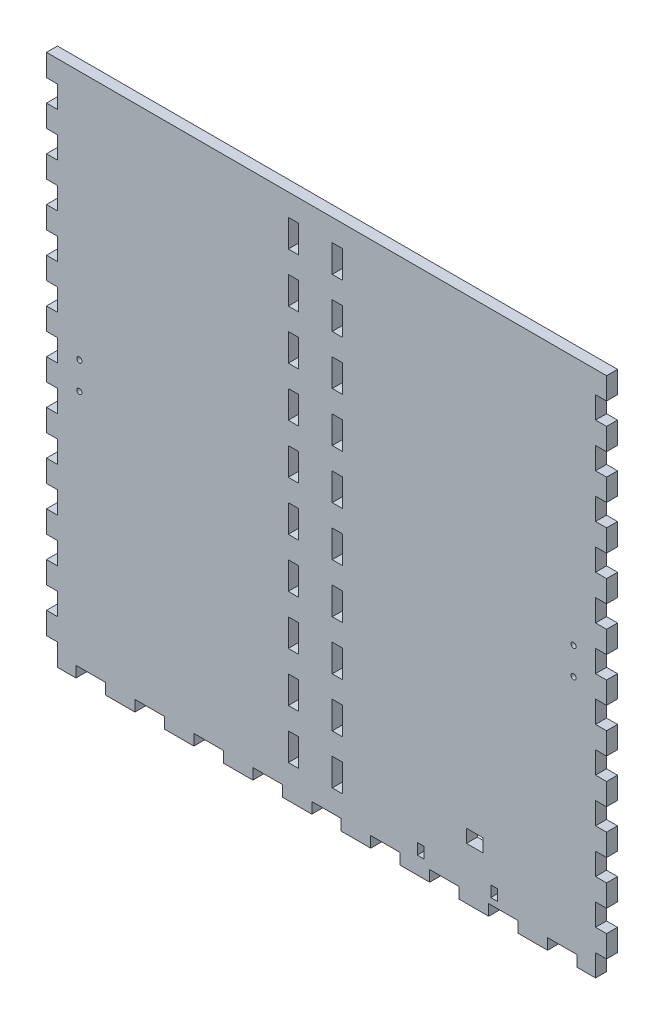
SolidWorks part; units mm, degrees
material "Acrylic (Medium-high impact)"
ref_plane "Front Plane" through (0, 0, 0) normal (0, 0, 1) x (1, 0, 0)
ref_plane "Top Plane" through (0, 0, 0) normal (0, 1, 0) x (1, 0, 0)
ref_plane "Right Plane" through (0, 0, 0) normal (1, 0, 0) x (0, 0, -1)
sketch "Sketch1" plane through (0, 0, 0) normal (0, 1, 0) x (1, 0, 0)
  line L1 (-161.925, 69.85) -> (161.925, 69.85)
  line L2 (-161.925, 69.85) -> (-161.925, -69.85)
  line L3 (-161.925, -69.85) -> (161.925, -69.85)
  line L4 (161.925, 69.85) -> (161.925, -69.85)
  point P4 (-161.925, 0)
  point P6 (0, 69.85)
  dimension "D1" = 139.7
  dimension "D2" = 323.85
extrude "Boss-Extrude1" add sketch "Sketch1" along normal blind 6.35
sketch "Sketch2" plane through (0, 6.35, 0) normal (0, 1, 0) x (1, 0, 0)
  line L0 (161.925, -69.85) -> (161.925, 69.85) construction
  line L1 (-161.925, 69.85) -> (161.925, 69.85)
  line L2 (-161.925, 69.85) -> (-161.925, -69.85)
  line L3 (-161.925, -69.85) -> (161.925, -69.85)
  line L4 (161.925, 69.85) -> (161.925, -69.85)
  line L5 (-161.925, -69.85) -> (161.925, -69.85) construction
  line L7 (-155.575, 63.5) -> (155.575, 63.5)
  line L8 (-155.575, 63.5) -> (-155.575, -63.5)
  line L9 (-155.575, -63.5) -> (155.575, -63.5)
  line L10 (155.575, 63.5) -> (155.575, -63.5)
  point P7 (-155.575, 0)
  point P14 (-161.925, 0)
  point P15 (0, -63.5)
  point P16 (0, -69.85)
  point P17 (155.575, 0)
  point P18 (161.925, 0)
  dimension "D1" = 6.35
  dimension "D2" = 6.35
extrude "Boss-Extrude2" add sketch "Sketch2" along normal blind 298.45
sketch "Sketch3" plane through (0, 0, 69.85) normal (0, 0, 1) x (1, 0, 0)
  line L0 (0, 304.8) -> (0, 0) construction
  line L2 (-155.575, 6.35) -> (155.575, 6.35) construction
  line L4 (-3.302, 283.21) -> (-3.302, 6.35)
  line L5 (-3.302, 6.35) -> (3.302, 6.35)
  line L6 (3.302, 292.354) -> (3.302, 6.35)
  line L7 (3.302, 292.354) -> (-16.256, 292.354)
  line L9 (-5.842, 285.75) -> (-16.256, 285.75)
  line L10 (-16.256, 292.354) -> (-16.256, 285.75)
  line L11 (3.302, 101.6) -> (16.002, 101.6) construction
  line L12 (-161.925, 0) -> (161.925, 0) construction
  line L13 (12.827, 88.9) -> (12.827, 101.6) construction
  line L14 (9.652, 88.9) -> (16.002, 88.9)
  line L15 (9.652, 88.9) -> (9.652, 71.9667)
  line L16 (9.652, 71.9667) -> (16.002, 71.9667)
  line L17 (16.002, 88.9) -> (16.002, 71.9667)
  line L18 (9.652, 42.3333) -> (16.002, 42.3333)
  line L19 (9.652, 42.3333) -> (9.652, 59.2667)
  line L20 (9.652, 59.2667) -> (16.002, 59.2667)
  line L21 (16.002, 42.3333) -> (16.002, 59.2667)
  line L26 (9.652, 29.6333) -> (16.002, 29.6333)
  line L27 (9.652, 29.6333) -> (9.652, 12.7)
  line L28 (9.652, 12.7) -> (16.002, 12.7)
  line L29 (16.002, 29.6333) -> (16.002, 12.7)
  line L30 (12.827, 59.2667) -> (12.827, 71.9667) construction
  line L31 (12.827, 29.6333) -> (12.827, 42.3333) construction
  line L32 (12.827, 12.7) -> (12.827, 0) construction
  line L33 (-161.925, 304.8) -> (161.925, 304.8) construction
  arc A0 (-3.302, 283.21) -> (-5.842, 285.75) centre (-5.842, 283.21) ccw
  point P4 (0, 0)
  point P5 (0, 6.35)
  dimension "D5" = 2.54
  dimension "D1" = 6.604
  dimension "D2" = 12.954
  dimension "D3" = 6.604
  dimension "D4" = 286.004
  dimension "D6" = 101.6
  dimension "D7" = 12.7
  dimension "D8" = 12.7
  dimension "D9" = 6.35
extrude "Door Slot" cut sketch "Sketch3" against normal blind 12.7
sketch "Sketch4" plane through (0, 0, -63.5) normal (0, 0, 1) x (1, 0, 0)
  line L0 (-161.925, 304.8) -> (161.925, 304.8) construction
  line L1 (-22.098, 304.8) -> (-16.256, 304.8)
  line L2 (-22.098, 304.8) -> (-22.098, 6.35)
  line L3 (-22.098, 6.35) -> (-16.256, 6.35)
  line L4 (-16.256, 304.8) -> (-16.256, 6.35)
  line L5 (6.223, 263.525) -> (6.223, 247.65) construction
  line L6 (-16.256, 292.354) -> (-16.256, 285.75) construction
  line L7 (3.302, 304.8) -> (9.144, 304.8)
  line L8 (3.302, 304.8) -> (3.302, 6.35)
  line L9 (3.302, 6.35) -> (9.144, 6.35)
  line L10 (9.144, 304.8) -> (9.144, 6.35)
  line L11 (155.575, 6.35) -> (-155.575, 6.35) construction
  line L12 (3.302, 6.35) -> (3.302, 292.354) construction
  line L13 (-16.256, 304.8) -> (-22.098, 304.8)
  line L14 (-16.256, 304.8) -> (-16.256, 292.1)
  line L15 (-16.256, 292.1) -> (-22.098, 292.1)
  line L16 (-22.098, 304.8) -> (-22.098, 292.1)
  line L17 (-16.256, 276.225) -> (-22.098, 276.225)
  line L18 (-16.256, 276.225) -> (-16.256, 263.525)
  line L19 (-16.256, 263.525) -> (-22.098, 263.525)
  line L20 (-22.098, 276.225) -> (-22.098, 263.525)
  line L21 (-22.098, 6.35) -> (-16.256, 6.35)
  line L22 (-22.098, 6.35) -> (-22.098, 19.05)
  line L23 (-22.098, 19.05) -> (-16.256, 19.05)
  line L24 (-16.256, 6.35) -> (-16.256, 19.05)
  line L25 (-22.098, 34.925) -> (-16.256, 34.925)
  line L26 (-22.098, 34.925) -> (-22.098, 47.625)
  line L27 (-22.098, 47.625) -> (-16.256, 47.625)
  line L28 (-16.256, 34.925) -> (-16.256, 47.625)
  line L29 (-22.098, 92.075) -> (-16.256, 92.075)
  line L30 (-22.098, 92.075) -> (-22.098, 104.775)
  line L31 (-22.098, 104.775) -> (-16.256, 104.775)
  line L32 (-16.256, 92.075) -> (-16.256, 104.775)
  line L33 (-22.098, 149.225) -> (-16.256, 149.225)
  line L34 (-22.098, 149.225) -> (-22.098, 161.925)
  line L35 (-22.098, 161.925) -> (-16.256, 161.925)
  line L36 (-16.256, 149.225) -> (-16.256, 161.925)
  line L37 (-22.098, 177.8) -> (-16.256, 177.8)
  line L38 (-22.098, 177.8) -> (-22.098, 190.5)
  line L39 (-22.098, 190.5) -> (-16.256, 190.5)
  line L40 (-16.256, 177.8) -> (-16.256, 190.5)
  line L41 (-22.098, 206.375) -> (-16.256, 206.375)
  line L42 (-22.098, 206.375) -> (-22.098, 219.075)
  line L43 (-22.098, 219.075) -> (-16.256, 219.075)
  line L44 (-16.256, 206.375) -> (-16.256, 219.075)
  line L45 (-22.098, 234.95) -> (-16.256, 234.95)
  line L46 (-22.098, 234.95) -> (-22.098, 247.65)
  line L47 (-22.098, 247.65) -> (-16.256, 247.65)
  line L48 (-16.256, 234.95) -> (-16.256, 247.65)
  line L49 (-16.256, 133.35) -> (-22.098, 133.35)
  line L50 (-16.256, 133.35) -> (-16.256, 120.65)
  line L51 (-16.256, 120.65) -> (-22.098, 120.65)
  line L52 (-22.098, 133.35) -> (-22.098, 120.65)
  line L53 (-16.256, 76.2) -> (-22.098, 76.2)
  line L54 (-16.256, 76.2) -> (-16.256, 63.5)
  line L55 (-16.256, 63.5) -> (-22.098, 63.5)
  line L56 (-22.098, 76.2) -> (-22.098, 63.5)
  line L57 (-19.177, 304.8) -> (-19.177, 292.1) construction
  line L58 (-19.177, 292.1) -> (-19.177, 276.225) construction
  line L59 (-19.177, 276.225) -> (-19.177, 263.525) construction
  line L60 (-19.177, 247.65) -> (-19.177, 234.95) construction
  line L61 (-19.177, 234.95) -> (-19.177, 219.075) construction
  line L62 (-19.177, 219.075) -> (-19.177, 206.375) construction
  line L63 (-19.177, 206.375) -> (-19.177, 190.5) construction
  line L64 (-19.177, 190.5) -> (-19.177, 177.8) construction
  line L65 (-19.177, 177.8) -> (-19.177, 161.925) construction
  line L66 (-19.177, 161.925) -> (-19.177, 149.225) construction
  line L67 (-19.177, 133.35) -> (-19.177, 120.65) construction
  line L68 (-19.177, 120.65) -> (-19.177, 104.775) construction
  line L69 (-19.177, 104.775) -> (-19.177, 92.075) construction
  line L70 (-19.177, 92.075) -> (-19.177, 76.2) construction
  line L71 (-19.177, 76.2) -> (-19.177, 63.5) construction
  line L72 (-19.177, 63.5) -> (-19.177, 47.625) construction
  line L73 (-19.177, 47.625) -> (-19.177, 34.925) construction
  line L74 (-19.177, 34.925) -> (-19.177, 19.05) construction
  line L75 (-19.177, 19.05) -> (-19.177, 6.35) construction
  line L76 (-19.177, 149.225) -> (-19.177, 133.35) construction
  line L77 (-19.177, 263.525) -> (-19.177, 247.65) construction
  line L78 (-6.477, 304.8) -> (-6.477, 0) construction
  line L79 (161.925, 304.8) -> (-161.925, 304.8) construction
  line L80 (161.925, 0) -> (-161.925, 0) construction
  line L81 (-6.477, 8.3493) -> (3.302, 8.3493) construction
  line L82 (-6.477, 8.3493) -> (-16.256, 8.3493) construction
  line L83 (6.223, 149.225) -> (6.223, 133.35) construction
  line L84 (6.223, 19.05) -> (6.223, 6.35) construction
  line L85 (6.223, 34.925) -> (6.223, 19.05) construction
  line L86 (6.223, 47.625) -> (6.223, 34.925) construction
  line L87 (6.223, 63.5) -> (6.223, 47.625) construction
  line L88 (6.223, 76.2) -> (6.223, 63.5) construction
  line L89 (6.223, 92.075) -> (6.223, 76.2) construction
  line L90 (6.223, 104.775) -> (6.223, 92.075) construction
  line L91 (6.223, 120.65) -> (6.223, 104.775) construction
  line L92 (6.223, 133.35) -> (6.223, 120.65) construction
  line L93 (6.223, 161.925) -> (6.223, 149.225) construction
  line L94 (6.223, 177.8) -> (6.223, 161.925) construction
  line L95 (6.223, 190.5) -> (6.223, 177.8) construction
  line L96 (6.223, 206.375) -> (6.223, 190.5) construction
  line L97 (6.223, 219.075) -> (6.223, 206.375) construction
  line L98 (6.223, 234.95) -> (6.223, 219.075) construction
  line L99 (6.223, 247.65) -> (6.223, 234.95) construction
  line L100 (6.223, 276.225) -> (6.223, 263.525) construction
  line L101 (6.223, 292.1) -> (6.223, 276.225) construction
  line L102 (6.223, 304.8) -> (6.223, 292.1) construction
  line L103 (9.144, 76.2) -> (9.144, 63.5)
  line L104 (3.302, 63.5) -> (9.144, 63.5)
  line L105 (3.302, 76.2) -> (3.302, 63.5)
  line L106 (3.302, 76.2) -> (9.144, 76.2)
  line L107 (9.144, 133.35) -> (9.144, 120.65)
  line L108 (3.302, 120.65) -> (9.144, 120.65)
  line L109 (3.302, 133.35) -> (3.302, 120.65)
  line L110 (3.302, 133.35) -> (9.144, 133.35)
  line L111 (3.302, 234.95) -> (3.302, 247.65)
  line L112 (9.144, 247.65) -> (3.302, 247.65)
  line L113 (9.144, 234.95) -> (9.144, 247.65)
  line L114 (9.144, 234.95) -> (3.302, 234.95)
  line L115 (3.302, 206.375) -> (3.302, 219.075)
  line L116 (9.144, 219.075) -> (3.302, 219.075)
  line L117 (9.144, 206.375) -> (9.144, 219.075)
  line L118 (9.144, 206.375) -> (3.302, 206.375)
  line L119 (3.302, 177.8) -> (3.302, 190.5)
  line L120 (9.144, 190.5) -> (3.302, 190.5)
  line L121 (9.144, 177.8) -> (9.144, 190.5)
  line L122 (9.144, 177.8) -> (3.302, 177.8)
  line L123 (3.302, 149.225) -> (3.302, 161.925)
  line L124 (9.144, 161.925) -> (3.302, 161.925)
  line L125 (9.144, 149.225) -> (9.144, 161.925)
  line L126 (9.144, 149.225) -> (3.302, 149.225)
  line L127 (3.302, 92.075) -> (3.302, 104.775)
  line L128 (9.144, 104.775) -> (3.302, 104.775)
  line L129 (9.144, 92.075) -> (9.144, 104.775)
  line L130 (9.144, 92.075) -> (3.302, 92.075)
  line L131 (3.302, 34.925) -> (3.302, 47.625)
  line L132 (9.144, 47.625) -> (3.302, 47.625)
  line L133 (9.144, 34.925) -> (9.144, 47.625)
  line L134 (9.144, 34.925) -> (3.302, 34.925)
  line L135 (3.302, 6.35) -> (3.302, 19.05)
  line L136 (9.144, 19.05) -> (3.302, 19.05)
  line L137 (9.144, 6.35) -> (9.144, 19.05)
  line L138 (9.144, 6.35) -> (3.302, 6.35)
  line L139 (9.144, 276.225) -> (9.144, 263.525)
  line L140 (3.302, 263.525) -> (9.144, 263.525)
  line L141 (3.302, 276.225) -> (3.302, 263.525)
  line L142 (3.302, 276.225) -> (9.144, 276.225)
  line L143 (9.144, 304.8) -> (9.144, 292.1)
  line L144 (3.302, 292.1) -> (9.144, 292.1)
  line L145 (3.302, 304.8) -> (3.302, 292.1)
  line L146 (3.302, 304.8) -> (9.144, 304.8)
  line L147 (3.302, 304.8) -> (3.302, 6.35)
  line L148 (9.144, 6.35) -> (3.302, 6.35)
  line L149 (9.144, 304.8) -> (9.144, 6.35)
  line L150 (9.144, 304.8) -> (3.302, 304.8)
  point P14 (-16.256, 289.052)
  dimension "D1" = 5.842
  dimension "D2" = 12.7
extrude "Door Guide Holes" cut sketch "Sketch4" against normal up to next contours L17 L4 L15 L2 | L2 L47 L4 L19 | L45 L2 L43 L4 | L41 L2 L39 L4 | L37 L2 L35 L4 | L49 L4 L33 L2 | L4 L51 L2 L31 | L53 L4 L29 L2 | L4 L55 L2 L27 | L25 L2 L23 L4 region at (-19.177, 284.1625, -63.5) region at (-19.177, 255.5875, -63.5) region at (-19.177, 227.0125, -63.5) region at (-19.177, 198.4375, -63.5) region at (-19.177, 169.8625, -63.5) region at (-19.177, 141.2875, -63.5) region at (-19.177, 112.7125, -63.5) region at (-19.177, 84.1375, -63.5) region at (-19.177, 55.5625, -63.5) region at (-19.177, 26.9875, -63.5)
ref_plane "Plane1" through (-6.477, 0, 0) normal (-1, 0, 0) x (0, 0, 1)
mirror "Mirror1" about plane through (-6.477, 0, 0) normal (-1, 0, 0) of "Door Guide Holes"
sketch "Lever Holes" plane through (0, 0, 69.85) normal (0, 0, 1) x (1, 0, 0)
  line L0 (80.899, 37.685) -> (90.551, 37.685)
  line L1 (80.899, 37.685) -> (80.899, 30.065)
  line L2 (80.899, 30.065) -> (90.551, 30.065)
  line L3 (90.551, 37.685) -> (90.551, 30.065)
  line L4 (52.475, 16.35) -> (56.475, 16.35)
  line L5 (52.475, 16.35) -> (52.475, 10)
  line L6 (52.475, 10) -> (56.475, 10)
  line L7 (56.475, 16.35) -> (56.475, 10)
  line L8 (94.975, 16.35) -> (98.975, 16.35)
  line L9 (94.975, 16.35) -> (94.975, 10)
  line L10 (94.975, 10) -> (98.975, 10)
  line L11 (98.975, 16.35) -> (98.975, 10)
  line L12 (56.475, 13.175) -> (94.975, 13.175) construction
  line L14 (3.302, 6.35) -> (155.575, 6.35) construction
  line L15 (155.575, 6.35) -> (-155.575, 6.35) construction
  line L16 (-142.875, 160.275) -> (-142.875, 144.525) construction
  line L17 (-161.925, 304.8) -> (-161.925, 0) construction
  line L18 (0, -76.835) -> (0, 76.835) construction
  line L19 (161.925, 304.8) -> (161.925, 0) construction
  circle A0 centre (-142.875, 160.275) radius 1.5
  circle A1 centre (-142.875, 144.525) radius 1.5
  circle A2 centre (142.875, 144.525) radius 1.5
  circle A3 centre (142.875, 160.275) radius 1.5
  point P13 (85.725, 30.065)
  point P17 (54.475, 16.35)
  point P31 (-142.875, 152.4)
  point P32 (-161.925, 152.4)
  dimension "D9" = 3
  dimension "D1" = 9.652
  dimension "D2" = 7.62
  dimension "D3" = 4
  dimension "D4" = 6.35
  dimension "D5" = 38.5
  dimension "D6" = 31.335
  dimension "D7" = 10
  dimension "D8" = 76.2
  dimension "D10" = 15.75
  dimension "D11" = 19.05
  dimension "D12" = 13.25
extrude "LeverHole Cut" cut sketch "Lever Holes" against normal through all
sketch "Sketch7" plane through (161.925, 0, 0) normal (1, 0, 0) x (0, 0, -1)
  line L0 (-37.211, 92.583) -> (37.211, 92.583)
  line L1 (-37.211, 92.583) -> (-37.211, 18.161)
  line L2 (-37.211, 18.161) -> (37.211, 18.161)
  line L3 (37.211, 92.583) -> (37.211, 18.161)
  line L4 (-69.85, 0) -> (69.85, 0) construction
  circle A0 centre (0, 55.372) radius 26.9875
  circle A1 centre (-37.211, 92.583) radius 3.175
  circle A2 centre (37.211, 92.583) radius 3.175
  circle A3 centre (-37.211, 18.161) radius 3.175
  circle A4 centre (37.211, 18.161) radius 3.175
  point P9 (0, 18.161)
  point P10 (-37.211, 55.372)
  dimension "D3" = 53.975
  dimension "D4" = 6.35
  dimension "D1" = 74.422
  dimension "D2" = 55.372
extrude "Cut-Extrude2" cut sketch "Sketch7" against normal up to next contours A0 | L0 A1 L1 | L1 A1 L0 | L3 A2 L0 | L0 A2 L3 | L2 A3 L1 | L1 A3 L2 | L2 A4 L3 | L3 A4 L2 region at (161.925, 93.0322, 37.6602) region at (161.925, 91.2355, 35.8635) region at (161.925, 93.0322, -37.6602) region at (161.925, 91.2355, -35.8635) region at (161.925, 19.5085, 35.8635) region at (161.925, 17.7118, 37.6602) region at (161.925, 17.7118, -37.6602) region at (161.925, 19.5085, -35.8635) region at (161.925, 55.372, 0)
sketch "Sketch8" plane through (-161.925, 0, 0) normal (-1, 0, 0) x (0, 0, 1)
  line L0 (-69.85, 0) -> (69.85, 0) construction
  circle A0 centre (0, 19.05) radius 3.175
  point P6 (0, 0)
  dimension "D1" = 6.35
  dimension "D2" = 19.05
extrude "Cut-Extrude3" cut sketch "Sketch8" against normal up to next
sketch "Bottom" plane through (0, 0, 0) normal (0, -1, 0) x (1, 0, 0)
  line L0 (-155.575, 63.5) -> (155.575, 63.5) construction
  line L1 (-161.925, 69.85) -> (-144.8803, 69.85)
  line L2 (-161.925, 69.85) -> (-161.925, 63.5)
  line L3 (-161.925, 63.5) -> (-144.8803, 63.5)
  line L4 (-144.8803, 69.85) -> (-144.8803, 63.5)
  line L5 (-144.8803, 69.85) -> (-127.8355, 69.85)
  line L6 (-144.8803, 69.85) -> (-144.8803, 63.5)
  line L7 (-144.8803, 63.5) -> (-127.8355, 63.5)
  line L8 (-127.8355, 69.85) -> (-127.8355, 63.5)
  line L9 (-127.8355, 69.85) -> (-110.7908, 69.85)
  line L10 (-127.8355, 69.85) -> (-127.8355, 63.5)
  line L11 (-127.8355, 63.5) -> (-110.7908, 63.5)
  line L12 (-110.7908, 69.85) -> (-110.7908, 63.5)
  line L13 (-110.7908, 69.85) -> (-93.7461, 69.85)
  line L14 (-110.7908, 69.85) -> (-110.7908, 63.5)
  line L15 (-110.7908, 63.5) -> (-93.7461, 63.5)
  line L16 (-93.7461, 69.85) -> (-93.7461, 63.5)
  line L17 (-161.925, 69.85) -> (161.925, 69.85) construction
  line L18 (-16.256, 63.5) -> (3.302, 63.5) construction
  line L19 (-93.7461, 69.85) -> (-76.7013, 69.85)
  line L20 (-93.7461, 69.85) -> (-93.7461, 63.5)
  line L21 (-93.7461, 63.5) -> (-76.7013, 63.5)
  line L22 (-76.7013, 69.85) -> (-76.7013, 63.5)
  line L23 (-76.7013, 69.85) -> (-59.6566, 69.85)
  line L24 (-76.7013, 69.85) -> (-76.7013, 63.5)
  line L25 (-76.7013, 63.5) -> (-59.6566, 63.5)
  line L26 (-59.6566, 69.85) -> (-59.6566, 63.5)
  line L27 (-59.6566, 69.85) -> (-42.6118, 69.85)
  line L28 (-59.6566, 69.85) -> (-59.6566, 63.5)
  line L29 (-59.6566, 63.5) -> (-42.6118, 63.5)
  line L30 (-42.6118, 69.85) -> (-42.6118, 63.5)
  line L31 (-42.6118, 69.85) -> (-25.5671, 69.85)
  line L32 (-42.6118, 69.85) -> (-42.6118, 63.5)
  line L33 (-42.6118, 63.5) -> (-25.5671, 63.5)
  line L34 (-25.5671, 69.85) -> (-25.5671, 63.5)
  line L36 (-25.5671, 69.85) -> (-8.5224, 69.85)
  line L37 (-25.5671, 69.85) -> (-25.5671, 63.5)
  line L38 (-25.5671, 63.5) -> (-8.5224, 63.5)
  line L39 (-8.5224, 69.85) -> (-8.5224, 63.5)
  line L40 (-8.5224, 69.85) -> (8.5224, 69.85)
  line L41 (-8.5224, 69.85) -> (-8.5224, 63.5)
  line L42 (-8.5224, 63.5) -> (8.5224, 63.5)
  line L43 (8.5224, 69.85) -> (8.5224, 63.5)
  line L44 (8.5224, 69.85) -> (25.5671, 69.85)
  line L45 (8.5224, 69.85) -> (8.5224, 63.5)
  line L46 (8.5224, 63.5) -> (25.5671, 63.5)
  line L47 (25.5671, 69.85) -> (25.5671, 63.5)
  line L48 (25.5671, 69.85) -> (42.6118, 69.85)
  line L49 (25.5671, 69.85) -> (25.5671, 63.5)
  line L50 (25.5671, 63.5) -> (42.6118, 63.5)
  line L51 (42.6118, 69.85) -> (42.6118, 63.5)
  line L52 (42.6118, 69.85) -> (59.6566, 69.85)
  line L53 (42.6118, 69.85) -> (42.6118, 63.5)
  line L54 (42.6118, 63.5) -> (59.6566, 63.5)
  line L55 (59.6566, 69.85) -> (59.6566, 63.5)
  line L56 (59.6566, 69.85) -> (76.7013, 69.85)
  line L57 (59.6566, 69.85) -> (59.6566, 63.5)
  line L58 (59.6566, 63.5) -> (76.7013, 63.5)
  line L59 (76.7013, 69.85) -> (76.7013, 63.5)
  line L60 (76.7013, 69.85) -> (93.7461, 69.85)
  line L61 (76.7013, 69.85) -> (76.7013, 63.5)
  line L62 (76.7013, 63.5) -> (93.7461, 63.5)
  line L63 (93.7461, 69.85) -> (93.7461, 63.5)
  line L64 (93.7461, 69.85) -> (110.7908, 69.85)
  line L65 (93.7461, 69.85) -> (93.7461, 63.5)
  line L66 (93.7461, 63.5) -> (110.7908, 63.5)
  line L67 (110.7908, 69.85) -> (110.7908, 63.5)
  line L68 (110.7908, 69.85) -> (127.8355, 69.85)
  line L69 (110.7908, 69.85) -> (110.7908, 63.5)
  line L70 (110.7908, 63.5) -> (127.8355, 63.5)
  line L71 (127.8355, 69.85) -> (127.8355, 63.5)
  line L72 (127.8355, 69.85) -> (144.8803, 69.85)
  line L73 (127.8355, 69.85) -> (127.8355, 63.5)
  line L74 (127.8355, 63.5) -> (144.8803, 63.5)
  line L75 (144.8803, 69.85) -> (144.8803, 63.5)
  line L76 (-155.575, -63.5) -> (-155.575, 63.5) construction
  line L77 (-161.925, 69.85) -> (-155.575, 69.85)
  line L78 (-161.925, 69.85) -> (-161.925, 57.15)
  line L79 (-161.925, 57.15) -> (-155.575, 57.15)
  line L80 (-155.575, 69.85) -> (-155.575, 57.15)
  line L82 (-161.925, 57.15) -> (-155.575, 57.15)
  line L83 (-161.925, 57.15) -> (-161.925, 44.45)
  line L84 (-161.925, 44.45) -> (-155.575, 44.45)
  line L85 (-155.575, 57.15) -> (-155.575, 44.45)
  line L86 (-161.925, 44.45) -> (-155.575, 44.45)
  line L87 (-161.925, 44.45) -> (-161.925, 31.75)
  line L88 (-161.925, 31.75) -> (-155.575, 31.75)
  line L89 (-155.575, 44.45) -> (-155.575, 31.75)
  line L90 (-161.925, 31.75) -> (-155.575, 31.75)
  line L91 (-161.925, 31.75) -> (-161.925, 19.05)
  line L92 (-161.925, 19.05) -> (-155.575, 19.05)
  line L93 (-155.575, 31.75) -> (-155.575, 19.05)
  line L94 (-161.925, 19.05) -> (-155.575, 19.05)
  line L95 (-161.925, 19.05) -> (-161.925, 6.35)
  line L96 (-161.925, 6.35) -> (-155.575, 6.35)
  line L97 (-155.575, 19.05) -> (-155.575, 6.35)
  line L98 (-161.925, 6.35) -> (-155.575, 6.35)
  line L99 (-161.925, 6.35) -> (-161.925, -6.35)
  line L100 (-161.925, -6.35) -> (-155.575, -6.35)
  line L101 (-155.575, 6.35) -> (-155.575, -6.35)
  line L102 (-161.925, -6.35) -> (-155.575, -6.35)
  line L103 (-161.925, -6.35) -> (-161.925, -19.05)
  line L104 (-161.925, -19.05) -> (-155.575, -19.05)
  line L105 (-155.575, -6.35) -> (-155.575, -19.05)
  line L106 (-161.925, -19.05) -> (-155.575, -19.05)
  line L107 (-161.925, -19.05) -> (-161.925, -31.75)
  line L108 (-161.925, -31.75) -> (-155.575, -31.75)
  line L109 (-155.575, -19.05) -> (-155.575, -31.75)
  line L110 (-161.925, -31.75) -> (-155.575, -31.75)
  line L111 (-161.925, -31.75) -> (-161.925, -44.45)
  line L112 (-161.925, -44.45) -> (-155.575, -44.45)
  line L113 (-155.575, -31.75) -> (-155.575, -44.45)
  line L114 (-161.925, -44.45) -> (-155.575, -44.45)
  line L115 (-161.925, -44.45) -> (-161.925, -57.15)
  line L116 (-161.925, -57.15) -> (-155.575, -57.15)
  line L117 (-155.575, -44.45) -> (-155.575, -57.15)
  line L118 (161.925, 69.85) -> (161.925, -69.85) construction
  line L119 (144.8803, 69.85) -> (161.925, 69.85)
  line L120 (144.8803, 69.85) -> (144.8803, 63.5)
  line L121 (144.8803, 63.5) -> (161.925, 63.5)
  line L122 (161.925, 69.85) -> (161.925, 63.5)
  line L123 (161.925, -69.85) -> (-161.925, -69.85) construction
  line L124 (-161.925, -57.15) -> (-155.575, -57.15)
  line L125 (-161.925, -57.15) -> (-161.925, -69.85)
  line L126 (-161.925, -69.85) -> (-155.575, -69.85)
  line L127 (-155.575, -57.15) -> (-155.575, -69.85)
  line L128 (167.64, 0) -> (-167.64, 0) construction
  line L129 (161.925, -69.85) -> (161.925, -63.5)
  line L130 (144.8803, -63.5) -> (161.925, -63.5)
  line L131 (144.8803, -69.85) -> (161.925, -69.85)
  line L132 (144.8803, -69.85) -> (144.8803, -63.5)
  line L133 (127.8355, -63.5) -> (144.8803, -63.5)
  line L134 (127.8355, -69.85) -> (144.8803, -69.85)
  line L135 (127.8355, -69.85) -> (127.8355, -63.5)
  line L136 (110.7908, -63.5) -> (127.8355, -63.5)
  line L137 (110.7908, -69.85) -> (127.8355, -69.85)
  line L138 (110.7908, -69.85) -> (110.7908, -63.5)
  line L139 (93.7461, -63.5) -> (110.7908, -63.5)
  line L140 (93.7461, -69.85) -> (110.7908, -69.85)
  line L141 (93.7461, -69.85) -> (93.7461, -63.5)
  line L142 (76.7013, -63.5) -> (93.7461, -63.5)
  line L143 (76.7013, -69.85) -> (93.7461, -69.85)
  line L144 (59.6566, -63.5) -> (76.7013, -63.5)
  line L145 (76.7013, -69.85) -> (76.7013, -63.5)
  line L146 (59.6566, -69.85) -> (76.7013, -69.85)
  line L147 (59.6566, -69.85) -> (59.6566, -63.5)
  line L148 (42.6118, -63.5) -> (59.6566, -63.5)
  line L149 (42.6118, -69.85) -> (59.6566, -69.85)
  line L150 (42.6118, -69.85) -> (42.6118, -63.5)
  line L151 (25.5671, -63.5) -> (42.6118, -63.5)
  line L152 (25.5671, -69.85) -> (42.6118, -69.85)
  line L153 (25.5671, -69.85) -> (25.5671, -63.5)
  line L154 (8.5224, -69.85) -> (25.5671, -69.85)
  line L155 (8.5224, -63.5) -> (25.5671, -63.5)
  line L156 (8.5224, -69.85) -> (8.5224, -63.5)
  line L157 (-8.5224, -63.5) -> (8.5224, -63.5)
  line L158 (-8.5224, -69.85) -> (8.5224, -69.85)
  line L159 (-25.5671, -63.5) -> (-8.5224, -63.5)
  line L160 (-8.5224, -69.85) -> (-8.5224, -63.5)
  line L161 (-25.5671, -69.85) -> (-8.5224, -69.85)
  line L162 (-25.5671, -69.85) -> (-25.5671, -63.5)
  line L163 (-42.6118, -63.5) -> (-25.5671, -63.5)
  line L164 (-42.6118, -69.85) -> (-25.5671, -69.85)
  line L165 (-42.6118, -69.85) -> (-42.6118, -63.5)
  line L166 (-59.6566, -63.5) -> (-42.6118, -63.5)
  line L167 (-59.6566, -69.85) -> (-42.6118, -69.85)
  line L168 (-59.6566, -69.85) -> (-59.6566, -63.5)
  line L169 (-76.7013, -69.85) -> (-59.6566, -69.85)
  line L170 (-76.7013, -63.5) -> (-59.6566, -63.5)
  line L171 (-93.7461, -63.5) -> (-76.7013, -63.5)
  line L172 (-76.7013, -69.85) -> (-76.7013, -63.5)
  line L173 (-93.7461, -69.85) -> (-76.7013, -69.85)
  line L174 (-110.7908, -69.85) -> (-93.7461, -69.85)
  line L175 (-110.7908, -63.5) -> (-93.7461, -63.5)
  line L176 (-93.7461, -69.85) -> (-93.7461, -63.5)
  line L177 (-127.8355, -69.85) -> (-127.8355, -63.5)
  line L178 (-127.8355, -69.85) -> (-110.7908, -69.85)
  line L179 (-110.7908, -69.85) -> (-110.7908, -63.5)
  line L180 (-127.8355, -63.5) -> (-110.7908, -63.5)
  line L181 (-144.8803, -63.5) -> (-127.8355, -63.5)
  line L182 (-144.8803, -69.85) -> (-127.8355, -69.85)
  line L183 (-144.8803, -69.85) -> (-144.8803, -63.5)
  line L184 (-161.925, -69.85) -> (-144.8803, -69.85)
  line L185 (-161.925, -69.85) -> (-161.925, -63.5)
  line L186 (-161.925, -63.5) -> (-144.8803, -63.5)
  line L187 (0, -76.835) -> (0, 76.835) construction
  line L188 (161.925, -69.85) -> (155.575, -69.85)
  line L189 (155.575, -57.15) -> (155.575, -69.85)
  line L190 (161.925, -57.15) -> (161.925, -69.85)
  line L191 (161.925, -57.15) -> (155.575, -57.15)
  line L192 (155.575, -44.45) -> (155.575, -57.15)
  line L193 (161.925, -44.45) -> (161.925, -57.15)
  line L194 (161.925, -44.45) -> (155.575, -44.45)
  line L195 (155.575, -31.75) -> (155.575, -44.45)
  line L196 (161.925, -31.75) -> (161.925, -44.45)
  line L197 (161.925, -31.75) -> (155.575, -31.75)
  line L198 (161.925, -19.05) -> (161.925, -31.75)
  line L199 (155.575, -19.05) -> (155.575, -31.75)
  line L200 (155.575, -6.35) -> (155.575, -19.05)
  line L201 (161.925, -6.35) -> (161.925, -19.05)
  line L202 (161.925, -19.05) -> (155.575, -19.05)
  line L203 (161.925, -6.35) -> (155.575, -6.35)
  line L204 (155.575, 6.35) -> (155.575, -6.35)
  line L205 (161.925, 6.35) -> (161.925, -6.35)
  line L206 (161.925, 6.35) -> (155.575, 6.35)
  line L207 (155.575, 19.05) -> (155.575, 6.35)
  line L208 (161.925, 19.05) -> (161.925, 6.35)
  line L209 (161.925, 19.05) -> (155.575, 19.05)
  line L210 (161.925, 31.75) -> (155.575, 31.75)
  line L211 (161.925, 44.45) -> (155.575, 44.45)
  line L212 (161.925, 57.15) -> (155.575, 57.15)
  line L213 (155.575, 31.75) -> (155.575, 19.05)
  line L214 (161.925, 31.75) -> (161.925, 19.05)
  line L215 (155.575, 44.45) -> (155.575, 31.75)
  line L216 (161.925, 44.45) -> (161.925, 31.75)
  line L217 (155.575, 57.15) -> (155.575, 44.45)
  line L218 (161.925, 57.15) -> (161.925, 44.45)
  line L219 (155.575, 69.85) -> (155.575, 57.15)
  line L220 (161.925, 69.85) -> (161.925, 57.15)
sketch "Front/Back" plane through (0, 0, 69.85) normal (0, 0, 1) x (1, 0, 0)
  line L0 (-155.575, 6.35) -> (-3.302, 6.35) construction
  line L1 (-161.925, 0) -> (-144.8803, 0)
  line L2 (-161.925, 0) -> (-161.925, 6.35)
  line L3 (-161.925, 6.35) -> (-144.8803, 6.35)
  line L4 (-144.8803, 0) -> (-144.8803, 6.35)
  line L5 (-161.925, 0) -> (161.925, 0) construction
  line L6 (-127.8355, 0) -> (-110.7908, 0) construction
  line L7 (-144.8803, 6.35) -> (-127.8355, 6.35)
  line L8 (-144.8803, 6.35) -> (-144.8803, 0)
  line L9 (-144.8803, 0) -> (-127.8355, 0)
  line L10 (-127.8355, 6.35) -> (-127.8355, 0)
  line L11 (-93.7461, 0) -> (-76.7013, 0) construction
  line L12 (-127.8355, 6.35) -> (-110.7908, 6.35)
  line L13 (-127.8355, 6.35) -> (-127.8355, 0)
  line L14 (-127.8355, 0) -> (-110.7908, 0)
  line L15 (-110.7908, 6.35) -> (-110.7908, 0)
  line L16 (-110.7908, 6.35) -> (-93.7461, 6.35)
  line L17 (-110.7908, 6.35) -> (-110.7908, 0)
  line L18 (-110.7908, 0) -> (-93.7461, 0)
  line L19 (-93.7461, 6.35) -> (-93.7461, 0)
  line L20 (-76.7013, 0) -> (-59.6566, 0) construction
  line L21 (-93.7461, 6.35) -> (-76.7013, 6.35)
  line L22 (-93.7461, 6.35) -> (-93.7461, 0)
  line L23 (-93.7461, 0) -> (-76.7013, 0)
  line L24 (-76.7013, 6.35) -> (-76.7013, 0)
  line L25 (-76.7013, 6.35) -> (-59.6566, 6.35)
  line L26 (-76.7013, 6.35) -> (-76.7013, 0)
  line L27 (-76.7013, 0) -> (-59.6566, 0)
  line L28 (-59.6566, 6.35) -> (-59.6566, 0)
  line L29 (-59.6566, 0) -> (-42.6118, 0) construction
  line L30 (-59.6566, 6.35) -> (-42.6118, 6.35)
  line L31 (-59.6566, 6.35) -> (-59.6566, 0)
  line L32 (-59.6566, 0) -> (-42.6118, 0)
  line L33 (-42.6118, 6.35) -> (-42.6118, 0)
  line L34 (-25.5671, 0) -> (-8.5224, 0) construction
  line L35 (-42.6118, 6.35) -> (-25.5671, 6.35)
  line L36 (-42.6118, 6.35) -> (-42.6118, 0)
  line L37 (-42.6118, 0) -> (-25.5671, 0)
  line L38 (-25.5671, 6.35) -> (-25.5671, 0)
  line L39 (8.5224, 0) -> (25.5671, 0) construction
  line L40 (-25.5671, 6.35) -> (-8.5224, 6.35)
  line L41 (-25.5671, 6.35) -> (-25.5671, 0)
  line L42 (-25.5671, 0) -> (-8.5224, 0)
  line L43 (-8.5224, 6.35) -> (-8.5224, 0)
  line L44 (-8.5224, 6.35) -> (8.5224, 6.35)
  line L45 (-8.5224, 6.35) -> (-8.5224, 0)
  line L46 (-8.5224, 0) -> (8.5224, 0)
  line L47 (8.5224, 6.35) -> (8.5224, 0)
  line L48 (8.5224, 0) -> (25.5671, 0) construction
  line L49 (42.6118, 0) -> (59.6566, 0) construction
  line L50 (8.5224, 6.35) -> (25.5671, 6.35)
  line L51 (8.5224, 6.35) -> (8.5224, 0)
  line L52 (8.5224, 0) -> (25.5671, 0)
  line L53 (25.5671, 6.35) -> (25.5671, 0)
  line L54 (25.5671, 6.35) -> (42.6118, 6.35)
  line L55 (25.5671, 6.35) -> (25.5671, 0)
  line L56 (25.5671, 0) -> (42.6118, 0)
  line L57 (42.6118, 6.35) -> (42.6118, 0)
  line L58 (76.7013, 0) -> (93.7461, 0) construction
  line L59 (42.6118, 6.35) -> (59.6566, 6.35)
  line L60 (42.6118, 6.35) -> (42.6118, 0)
  line L61 (42.6118, 0) -> (59.6566, 0)
  line L62 (59.6566, 6.35) -> (59.6566, 0)
  line L63 (59.6566, 6.35) -> (76.7013, 6.35)
  line L64 (59.6566, 6.35) -> (59.6566, 0)
  line L65 (59.6566, 0) -> (76.7013, 0)
  line L66 (76.7013, 6.35) -> (76.7013, 0)
  line L67 (59.6566, 0) -> (76.7013, 0) construction
  line L68 (110.7908, 0) -> (127.8355, 0) construction
  line L69 (76.7013, 6.35) -> (93.7461, 6.35)
  line L70 (76.7013, 6.35) -> (76.7013, 0)
  line L71 (76.7013, 0) -> (93.7461, 0)
  line L72 (93.7461, 6.35) -> (93.7461, 0)
  line L73 (93.7461, 6.35) -> (110.7908, 6.35)
  line L74 (93.7461, 6.35) -> (93.7461, 0)
  line L75 (93.7461, 0) -> (110.7908, 0)
  line L76 (110.7908, 6.35) -> (110.7908, 0)
  line L77 (127.8355, 0) -> (144.8803, 0) construction
  line L78 (110.7908, 6.35) -> (127.8355, 6.35)
  line L79 (110.7908, 6.35) -> (110.7908, 0)
  line L80 (110.7908, 0) -> (127.8355, 0)
  line L81 (127.8355, 6.35) -> (127.8355, 0)
  line L82 (127.8355, 0) -> (144.8803, 0) construction
  line L84 (127.8355, 6.35) -> (144.8803, 6.35)
  line L85 (127.8355, 6.35) -> (127.8355, 0)
  line L86 (127.8355, 0) -> (144.8803, 0)
  line L87 (144.8803, 6.35) -> (144.8803, 0)
  line L88 (144.8803, 6.35) -> (161.925, 6.35)
  line L89 (144.8803, 6.35) -> (144.8803, 0)
  line L90 (144.8803, 0) -> (161.925, 0)
  line L91 (161.925, 6.35) -> (161.925, 0)
  line L92 (-155.575, 304.8) -> (-155.575, 6.35) construction
  line L93 (-161.925, 0) -> (-155.575, 0)
  line L94 (-161.925, 0) -> (-161.925, 12.7)
  line L95 (-161.925, 12.7) -> (-155.575, 12.7)
  line L96 (-155.575, 0) -> (-155.575, 12.7)
  line L97 (-161.925, 304.8) -> (-161.925, 0) construction
  line L98 (-161.925, 12.7) -> (-155.575, 12.7)
  line L99 (-161.925, 12.7) -> (-161.925, 25.4)
  line L100 (-161.925, 25.4) -> (-155.575, 25.4)
  line L101 (-155.575, 12.7) -> (-155.575, 25.4)
  line L102 (-161.925, 25.4) -> (-155.575, 25.4)
  line L103 (-161.925, 25.4) -> (-161.925, 38.1)
  line L104 (-161.925, 38.1) -> (-155.575, 38.1)
  line L105 (-155.575, 25.4) -> (-155.575, 38.1)
  line L106 (-161.925, 38.1) -> (-155.575, 38.1)
  line L107 (-161.925, 38.1) -> (-161.925, 50.8)
  line L108 (-161.925, 50.8) -> (-155.575, 50.8)
  line L109 (-155.575, 38.1) -> (-155.575, 50.8)
  line L110 (-161.925, 50.8) -> (-155.575, 50.8)
  line L111 (-161.925, 50.8) -> (-161.925, 63.5)
  line L112 (-161.925, 63.5) -> (-155.575, 63.5)
  line L113 (-155.575, 50.8) -> (-155.575, 63.5)
  line L114 (-161.925, 63.5) -> (-155.575, 63.5)
  line L115 (-161.925, 63.5) -> (-161.925, 76.2)
  line L116 (-161.925, 76.2) -> (-155.575, 76.2)
  line L117 (-155.575, 63.5) -> (-155.575, 76.2)
  line L118 (-161.925, 76.2) -> (-155.575, 76.2)
  line L119 (-161.925, 76.2) -> (-161.925, 88.9)
  line L120 (-161.925, 88.9) -> (-155.575, 88.9)
  line L121 (-155.575, 76.2) -> (-155.575, 88.9)
  line L122 (-161.925, 88.9) -> (-155.575, 88.9)
  line L123 (-161.925, 88.9) -> (-161.925, 101.6)
  line L124 (-161.925, 101.6) -> (-155.575, 101.6)
  line L125 (-155.575, 88.9) -> (-155.575, 101.6)
  line L126 (-161.925, 101.6) -> (-155.575, 101.6)
  line L127 (-161.925, 101.6) -> (-161.925, 114.3)
  line L128 (-161.925, 114.3) -> (-155.575, 114.3)
  line L129 (-155.575, 101.6) -> (-155.575, 114.3)
  line L130 (-161.925, 114.3) -> (-155.575, 114.3)
  line L131 (-161.925, 114.3) -> (-161.925, 127)
  line L132 (-161.925, 127) -> (-155.575, 127)
  line L133 (-155.575, 114.3) -> (-155.575, 127)
  line L134 (-161.925, 127) -> (-155.575, 127)
  line L135 (-161.925, 127) -> (-161.925, 139.7)
  line L136 (-161.925, 139.7) -> (-155.575, 139.7)
  line L137 (-155.575, 127) -> (-155.575, 139.7)
  line L138 (-161.925, 139.7) -> (-155.575, 139.7)
  line L139 (-161.925, 139.7) -> (-161.925, 152.4)
  line L140 (-161.925, 152.4) -> (-155.575, 152.4)
  line L141 (-155.575, 139.7) -> (-155.575, 152.4)
  line L142 (-161.925, 152.4) -> (-155.575, 152.4)
  line L143 (-161.925, 152.4) -> (-161.925, 165.1)
  line L144 (-161.925, 165.1) -> (-155.575, 165.1)
  line L145 (-155.575, 152.4) -> (-155.575, 165.1)
  line L146 (-161.925, 165.1) -> (-155.575, 165.1)
  line L147 (-161.925, 165.1) -> (-161.925, 177.8)
  line L148 (-161.925, 177.8) -> (-155.575, 177.8)
  line L149 (-155.575, 165.1) -> (-155.575, 177.8)
  line L150 (-161.925, 177.8) -> (-155.575, 177.8)
  line L151 (-161.925, 177.8) -> (-161.925, 190.5)
  line L152 (-161.925, 190.5) -> (-155.575, 190.5)
  line L153 (-155.575, 177.8) -> (-155.575, 190.5)
  line L154 (-161.925, 190.5) -> (-155.575, 190.5)
  line L155 (-161.925, 190.5) -> (-161.925, 203.2)
  line L156 (-161.925, 203.2) -> (-155.575, 203.2)
  line L157 (-155.575, 190.5) -> (-155.575, 203.2)
  line L158 (-161.925, 203.2) -> (-155.575, 203.2)
  line L159 (-161.925, 203.2) -> (-161.925, 215.9)
  line L160 (-161.925, 215.9) -> (-155.575, 215.9)
  line L161 (-155.575, 203.2) -> (-155.575, 215.9)
  line L162 (-161.925, 215.9) -> (-155.575, 215.9)
  line L163 (-161.925, 215.9) -> (-161.925, 228.6)
  line L164 (-161.925, 228.6) -> (-155.575, 228.6)
  line L165 (-155.575, 215.9) -> (-155.575, 228.6)
  line L166 (-161.925, 228.6) -> (-155.575, 228.6)
  line L167 (-161.925, 228.6) -> (-161.925, 241.3)
  line L168 (-161.925, 241.3) -> (-155.575, 241.3)
  line L169 (-155.575, 228.6) -> (-155.575, 241.3)
  line L170 (-161.925, 241.3) -> (-155.575, 241.3)
  line L171 (-161.925, 241.3) -> (-161.925, 254)
  line L172 (-161.925, 254) -> (-155.575, 254)
  line L173 (-155.575, 241.3) -> (-155.575, 254)
  line L174 (-161.925, 254) -> (-155.575, 254)
  line L175 (-161.925, 254) -> (-161.925, 266.7)
  line L176 (-161.925, 266.7) -> (-155.575, 266.7)
  line L177 (-155.575, 254) -> (-155.575, 266.7)
  line L178 (-161.925, 266.7) -> (-155.575, 266.7)
  line L179 (-161.925, 266.7) -> (-161.925, 279.4)
  line L180 (-161.925, 279.4) -> (-155.575, 279.4)
  line L181 (-155.575, 266.7) -> (-155.575, 279.4)
  line L182 (-161.925, 279.4) -> (-155.575, 279.4)
  line L183 (-161.925, 279.4) -> (-161.925, 292.1)
  line L184 (-161.925, 292.1) -> (-155.575, 292.1)
  line L185 (-155.575, 279.4) -> (-155.575, 292.1)
  line L186 (-161.925, 292.1) -> (-155.575, 292.1)
  line L187 (-161.925, 292.1) -> (-161.925, 304.8)
  line L188 (-161.925, 304.8) -> (-155.575, 304.8)
  line L189 (-155.575, 292.1) -> (-155.575, 304.8)
  line L190 (-161.925, 304.8) -> (-155.575, 304.8)
  line L194 (-161.925, 304.8) -> (161.925, 304.8) construction
  line L195 (0, -76.835) -> (0, 76.835) construction
  line L196 (161.925, 304.8) -> (155.575, 304.8)
  line L197 (155.575, 292.1) -> (155.575, 304.8)
  line L198 (161.925, 304.8) -> (155.575, 304.8)
  line L199 (161.925, 292.1) -> (161.925, 304.8)
  line L200 (161.925, 292.1) -> (155.575, 292.1)
  line L201 (155.575, 279.4) -> (155.575, 292.1)
  line L202 (161.925, 292.1) -> (155.575, 292.1)
  line L203 (161.925, 279.4) -> (161.925, 292.1)
  line L204 (161.925, 279.4) -> (155.575, 279.4)
  line L205 (155.575, 266.7) -> (155.575, 279.4)
  line L206 (161.925, 279.4) -> (155.575, 279.4)
  line L207 (161.925, 266.7) -> (161.925, 279.4)
  line L208 (161.925, 266.7) -> (155.575, 266.7)
  line L209 (155.575, 254) -> (155.575, 266.7)
  line L210 (161.925, 266.7) -> (155.575, 266.7)
  line L211 (161.925, 254) -> (161.925, 266.7)
  line L212 (161.925, 254) -> (155.575, 254)
  line L213 (155.575, 241.3) -> (155.575, 254)
  line L214 (161.925, 254) -> (155.575, 254)
  line L215 (161.925, 241.3) -> (161.925, 254)
  line L216 (161.925, 241.3) -> (155.575, 241.3)
  line L217 (155.575, 228.6) -> (155.575, 241.3)
  line L218 (161.925, 241.3) -> (155.575, 241.3)
  line L219 (161.925, 228.6) -> (161.925, 241.3)
  line L220 (161.925, 228.6) -> (155.575, 228.6)
  line L221 (155.575, 215.9) -> (155.575, 228.6)
  line L222 (161.925, 228.6) -> (155.575, 228.6)
  line L223 (161.925, 215.9) -> (161.925, 228.6)
  line L224 (161.925, 215.9) -> (155.575, 215.9)
  line L225 (155.575, 203.2) -> (155.575, 215.9)
  line L226 (161.925, 215.9) -> (155.575, 215.9)
  line L227 (161.925, 203.2) -> (161.925, 215.9)
  line L228 (161.925, 203.2) -> (155.575, 203.2)
  line L229 (155.575, 190.5) -> (155.575, 203.2)
  line L230 (161.925, 203.2) -> (155.575, 203.2)
  line L231 (161.925, 190.5) -> (161.925, 203.2)
  line L232 (161.925, 190.5) -> (155.575, 190.5)
  line L233 (155.575, 177.8) -> (155.575, 190.5)
  line L234 (161.925, 190.5) -> (155.575, 190.5)
  line L235 (161.925, 177.8) -> (161.925, 190.5)
  line L236 (161.925, 177.8) -> (155.575, 177.8)
  line L237 (155.575, 165.1) -> (155.575, 177.8)
  line L238 (161.925, 177.8) -> (155.575, 177.8)
  line L239 (161.925, 165.1) -> (161.925, 177.8)
  line L240 (161.925, 165.1) -> (155.575, 165.1)
  line L241 (155.575, 152.4) -> (155.575, 165.1)
  line L242 (161.925, 165.1) -> (155.575, 165.1)
  line L243 (161.925, 152.4) -> (161.925, 165.1)
  line L244 (161.925, 152.4) -> (155.575, 152.4)
  line L245 (155.575, 139.7) -> (155.575, 152.4)
  line L246 (161.925, 152.4) -> (155.575, 152.4)
  line L247 (161.925, 139.7) -> (161.925, 152.4)
  line L248 (161.925, 139.7) -> (155.575, 139.7)
  line L249 (155.575, 127) -> (155.575, 139.7)
  line L250 (161.925, 139.7) -> (155.575, 139.7)
  line L251 (161.925, 127) -> (161.925, 139.7)
  line L252 (161.925, 127) -> (155.575, 127)
  line L253 (155.575, 114.3) -> (155.575, 127)
  line L254 (161.925, 127) -> (155.575, 127)
  line L255 (161.925, 114.3) -> (161.925, 127)
  line L256 (161.925, 114.3) -> (155.575, 114.3)
  line L257 (155.575, 101.6) -> (155.575, 114.3)
  line L258 (161.925, 114.3) -> (155.575, 114.3)
  line L259 (161.925, 101.6) -> (161.925, 114.3)
  line L260 (161.925, 101.6) -> (155.575, 101.6)
  line L261 (155.575, 88.9) -> (155.575, 101.6)
  line L262 (161.925, 101.6) -> (155.575, 101.6)
  line L263 (161.925, 88.9) -> (161.925, 101.6)
  line L264 (161.925, 88.9) -> (155.575, 88.9)
  line L265 (155.575, 76.2) -> (155.575, 88.9)
  line L266 (161.925, 88.9) -> (155.575, 88.9)
  line L267 (161.925, 76.2) -> (161.925, 88.9)
  line L268 (161.925, 76.2) -> (155.575, 76.2)
  line L269 (155.575, 63.5) -> (155.575, 76.2)
  line L270 (161.925, 76.2) -> (155.575, 76.2)
  line L271 (161.925, 63.5) -> (161.925, 76.2)
  line L272 (161.925, 63.5) -> (155.575, 63.5)
  line L273 (155.575, 50.8) -> (155.575, 63.5)
  line L274 (161.925, 63.5) -> (155.575, 63.5)
  line L275 (161.925, 50.8) -> (161.925, 63.5)
  line L276 (161.925, 50.8) -> (155.575, 50.8)
  line L277 (155.575, 38.1) -> (155.575, 50.8)
  line L278 (161.925, 50.8) -> (155.575, 50.8)
  line L279 (161.925, 38.1) -> (161.925, 50.8)
  line L280 (161.925, 38.1) -> (155.575, 38.1)
  line L281 (155.575, 25.4) -> (155.575, 38.1)
  line L282 (161.925, 38.1) -> (155.575, 38.1)
  line L283 (161.925, 25.4) -> (161.925, 38.1)
  line L284 (161.925, 25.4) -> (155.575, 25.4)
  line L285 (155.575, 12.7) -> (155.575, 25.4)
  line L286 (161.925, 25.4) -> (155.575, 25.4)
  line L287 (161.925, 12.7) -> (161.925, 25.4)
  line L288 (161.925, 12.7) -> (155.575, 12.7)
  line L289 (155.575, 0) -> (155.575, 12.7)
  line L290 (161.925, 12.7) -> (155.575, 12.7)
  line L291 (161.925, 0) -> (161.925, 12.7)
  line L292 (161.925, 0) -> (155.575, 0)
  line L293 (161.925, 0) -> (161.925, 6.35)
  line M74 (3.302, 6.35) -> (-3.302, 6.35)
  line M91 (-161.925, 0) -> (161.925, 0)
  line M92 (161.925, 0) -> (161.925, 304.8)
  line M94 (-161.925, 304.8) -> (-161.925, 0)
sketch "Left/Right" plane through (-161.925, 0, 0) normal (-1, 0, 0) x (0, 0, 1)
  line L0 (57.15, 0) -> (44.45, 0) construction
  line L8 (57.15, 0) -> (57.15, 6.35)
  line L9 (57.15, 6.35) -> (44.45, 6.35)
  line L10 (57.15, 6.35) -> (57.15, 0)
  line L11 (57.15, 0) -> (44.45, 0)
  line L12 (44.45, 6.35) -> (44.45, 0)
  line L13 (-69.85, 0) -> (69.85, 0) construction
  line L14 (44.45, 0) -> (31.75, 0) construction
  line L15 (44.45, 6.35) -> (31.75, 6.35)
  line L16 (44.45, 6.35) -> (44.45, 0)
  line L17 (44.45, 0) -> (31.75, 0)
  line L18 (31.75, 6.35) -> (31.75, 0)
  line L19 (31.75, 0) -> (19.05, 0) construction
  line L20 (31.75, 6.35) -> (19.05, 6.35)
  line L21 (31.75, 6.35) -> (31.75, 0)
  line L22 (31.75, 0) -> (19.05, 0)
  line L23 (19.05, 6.35) -> (19.05, 0)
  line L24 (19.05, 0) -> (6.35, 0) construction
  line L25 (19.05, 6.35) -> (6.35, 6.35)
  line L26 (19.05, 6.35) -> (19.05, 0)
  line L27 (19.05, 0) -> (6.35, 0)
  line L28 (6.35, 6.35) -> (6.35, 0)
  line L29 (6.35, 0) -> (-6.35, 0) construction
  line L30 (6.35, 6.35) -> (-6.35, 6.35)
  line L31 (6.35, 6.35) -> (6.35, 0)
  line L32 (6.35, 0) -> (-6.35, 0)
  line L33 (-6.35, 6.35) -> (-6.35, 0)
  line L34 (-6.35, 0) -> (-19.05, 0) construction
  line L35 (-6.35, 6.35) -> (-19.05, 6.35)
  line L36 (-6.35, 6.35) -> (-6.35, 0)
  line L37 (-6.35, 0) -> (-19.05, 0)
  line L38 (-19.05, 6.35) -> (-19.05, 0)
  line L39 (-19.05, 0) -> (-31.75, 0) construction
  line L40 (-19.05, 6.35) -> (-31.75, 6.35)
  line L41 (-19.05, 6.35) -> (-19.05, 0)
  line L42 (-19.05, 0) -> (-31.75, 0)
  line L43 (-31.75, 6.35) -> (-31.75, 0)
  line L44 (-19.05, 0) -> (-31.75, 0) construction
  line L45 (-31.75, 0) -> (-44.45, 0) construction
  line L46 (-31.75, 6.35) -> (-44.45, 6.35)
  line L47 (-31.75, 6.35) -> (-31.75, 0)
  line L48 (-31.75, 0) -> (-44.45, 0)
  line L49 (-44.45, 6.35) -> (-44.45, 0)
  line L50 (69.85, 304.8) -> (69.85, 0) construction
  line L51 (-44.45, 6.35) -> (-57.15, 6.35)
  line L52 (-44.45, 6.35) -> (-44.45, 0)
  line L53 (-44.45, 0) -> (-57.15, 0)
  line L55 (-69.85, 0) -> (-63.5, 0) construction
  line L57 (-57.15, 6.35) -> (-57.15, 0)
  line L60 (-69.85, 0) -> (-63.5, 0) construction
  line L61 (69.85, 0) -> (57.15, 0) construction
  line L63 (-69.85, 6.35) -> (-69.85, 0)
  line L65 (57.15, 6.35) -> (69.85, 6.35)
  line L66 (57.15, 6.35) -> (57.15, 0)
  line L67 (57.15, 0) -> (69.85, 0)
  line L68 (69.85, 6.35) -> (69.85, 0)
  line L69 (69.85, 165.1) -> (69.85, 177.8) construction
  line L70 (63.5, 12.7) -> (69.85, 12.7)
  line L71 (63.5, 12.7) -> (63.5, 25.4)
  line L72 (63.5, 25.4) -> (69.85, 25.4)
  line L73 (-57.15, 0) -> (-69.85, 0)
  line L74 (-69.85, 6.35) -> (-57.15, 6.35)
  line L75 (-57.15, 0) -> (-69.85, 0) construction
  line L76 (69.85, 12.7) -> (69.85, 25.4)
  line L77 (69.85, 0) -> (63.5, 0)
  line L78 (69.85, 0) -> (69.85, 12.7)
  line L79 (69.85, 12.7) -> (63.5, 12.7)
  line L80 (63.5, 0) -> (63.5, 12.7)
  line L81 (63.5, 25.4) -> (69.85, 25.4)
  line L82 (63.5, 25.4) -> (63.5, 38.1)
  line L83 (63.5, 38.1) -> (69.85, 38.1)
  line L84 (69.85, 25.4) -> (69.85, 38.1)
  line L85 (63.5, 38.1) -> (69.85, 38.1)
  line L86 (63.5, 38.1) -> (63.5, 50.8)
  line L87 (63.5, 50.8) -> (69.85, 50.8)
  line L88 (69.85, 38.1) -> (69.85, 50.8)
  line L89 (63.5, 50.8) -> (69.85, 50.8)
  line L90 (63.5, 50.8) -> (63.5, 63.5)
  line L91 (63.5, 63.5) -> (69.85, 63.5)
  line L92 (69.85, 50.8) -> (69.85, 63.5)
  line L93 (63.5, 63.5) -> (69.85, 63.5)
  line L94 (63.5, 63.5) -> (63.5, 76.2)
  line L95 (63.5, 76.2) -> (69.85, 76.2)
  line L96 (69.85, 63.5) -> (69.85, 76.2)
  line L97 (63.5, 76.2) -> (69.85, 76.2)
  line L98 (63.5, 76.2) -> (63.5, 88.9)
  line L99 (63.5, 88.9) -> (69.85, 88.9)
  line L100 (69.85, 76.2) -> (69.85, 88.9)
  line L101 (63.5, 88.9) -> (69.85, 88.9)
  line L102 (63.5, 88.9) -> (63.5, 101.6)
  line L103 (63.5, 101.6) -> (69.85, 101.6)
  line L104 (69.85, 88.9) -> (69.85, 101.6)
  line L105 (63.5, 101.6) -> (69.85, 101.6)
  line L106 (63.5, 101.6) -> (63.5, 114.3)
  line L107 (63.5, 114.3) -> (69.85, 114.3)
  line L108 (69.85, 101.6) -> (69.85, 114.3)
  line L109 (63.5, 114.3) -> (69.85, 114.3)
  line L110 (63.5, 114.3) -> (63.5, 127)
  line L111 (63.5, 127) -> (69.85, 127)
  line L112 (69.85, 114.3) -> (69.85, 127)
  line L113 (63.5, 127) -> (69.85, 127)
  line L114 (63.5, 127) -> (63.5, 139.7)
  line L115 (63.5, 139.7) -> (69.85, 139.7)
  line L116 (69.85, 127) -> (69.85, 139.7)
  line L117 (63.5, 139.7) -> (69.85, 139.7)
  line L118 (63.5, 139.7) -> (63.5, 152.4)
  line L119 (63.5, 152.4) -> (69.85, 152.4)
  line L120 (69.85, 139.7) -> (69.85, 152.4)
  line L121 (63.5, 152.4) -> (69.85, 152.4)
  line L122 (63.5, 152.4) -> (63.5, 165.1)
  line L123 (63.5, 165.1) -> (69.85, 165.1)
  line L124 (69.85, 152.4) -> (69.85, 165.1)
  line L125 (63.5, 165.1) -> (69.85, 165.1)
  line L126 (63.5, 165.1) -> (63.5, 177.8)
  line L127 (63.5, 177.8) -> (69.85, 177.8)
  line L128 (69.85, 165.1) -> (69.85, 177.8)
  line L129 (63.5, 177.8) -> (69.85, 177.8)
  line L130 (63.5, 177.8) -> (63.5, 190.5)
  line L131 (63.5, 190.5) -> (69.85, 190.5)
  line L132 (69.85, 177.8) -> (69.85, 190.5)
  line L133 (69.85, 203.2) -> (69.85, 215.9) construction
  line L134 (63.5, 190.5) -> (69.85, 190.5)
  line L135 (63.5, 190.5) -> (63.5, 203.2)
  line L136 (63.5, 203.2) -> (69.85, 203.2)
  line L137 (69.85, 190.5) -> (69.85, 203.2)
  line L138 (63.5, 203.2) -> (69.85, 203.2)
  line L139 (63.5, 203.2) -> (63.5, 215.9)
  line L140 (63.5, 215.9) -> (69.85, 215.9)
  line L141 (69.85, 203.2) -> (69.85, 215.9)
  line L142 (63.5, 215.9) -> (69.85, 215.9)
  line L143 (63.5, 215.9) -> (63.5, 228.6)
  line L144 (63.5, 228.6) -> (69.85, 228.6)
  line L145 (69.85, 215.9) -> (69.85, 228.6)
  line L146 (69.85, 215.9) -> (69.85, 228.6) construction
  line L147 (63.5, 228.6) -> (69.85, 228.6)
  line L148 (63.5, 228.6) -> (63.5, 241.3)
  line L149 (63.5, 241.3) -> (69.85, 241.3)
  line L150 (69.85, 228.6) -> (69.85, 241.3)
  line L151 (0, -167.64) -> (0, 167.64) construction
  line L152 (63.5, 241.3) -> (69.85, 241.3)
  line L153 (63.5, 241.3) -> (63.5, 254)
  line L154 (63.5, 254) -> (69.85, 254)
  line L155 (69.85, 241.3) -> (69.85, 254)
  line L156 (63.5, 254) -> (69.85, 254)
  line L157 (63.5, 254) -> (63.5, 266.7)
  line L158 (63.5, 266.7) -> (69.85, 266.7)
  line L159 (69.85, 254) -> (69.85, 266.7)
  line L160 (63.5, 266.7) -> (69.85, 266.7)
  line L161 (63.5, 266.7) -> (63.5, 279.4)
  line L162 (63.5, 279.4) -> (69.85, 279.4)
  line L163 (69.85, 266.7) -> (69.85, 279.4)
  line L164 (63.5, 279.4) -> (69.85, 279.4)
  line L165 (63.5, 279.4) -> (63.5, 292.1)
  line L166 (63.5, 292.1) -> (69.85, 292.1)
  line L167 (69.85, 279.4) -> (69.85, 292.1)
  line L168 (63.5, 292.1) -> (69.85, 292.1)
  line L169 (63.5, 292.1) -> (63.5, 304.8)
  line L170 (63.5, 304.8) -> (69.85, 304.8)
  line L171 (69.85, 292.1) -> (69.85, 304.8)
  line L172 (-69.85, 292.1) -> (-69.85, 304.8)
  line L173 (-63.5, 304.8) -> (-69.85, 304.8)
  line L174 (-63.5, 292.1) -> (-63.5, 304.8)
  line L175 (-63.5, 292.1) -> (-69.85, 292.1)
  line L176 (-69.85, 279.4) -> (-69.85, 292.1)
  line L177 (-63.5, 292.1) -> (-69.85, 292.1)
  line L178 (-63.5, 279.4) -> (-63.5, 292.1)
  line L179 (-63.5, 279.4) -> (-69.85, 279.4)
  line L180 (-69.85, 266.7) -> (-69.85, 279.4)
  line L181 (-63.5, 279.4) -> (-69.85, 279.4)
  line L182 (-63.5, 266.7) -> (-63.5, 279.4)
  line L183 (-63.5, 266.7) -> (-69.85, 266.7)
  line L184 (-69.85, 254) -> (-69.85, 266.7)
  line L185 (-63.5, 266.7) -> (-69.85, 266.7)
  line L186 (-63.5, 254) -> (-63.5, 266.7)
  line L187 (-63.5, 254) -> (-69.85, 254)
  line L188 (-69.85, 241.3) -> (-69.85, 254)
  line L189 (-63.5, 254) -> (-69.85, 254)
  line L190 (-63.5, 241.3) -> (-63.5, 254)
  line L191 (-63.5, 241.3) -> (-69.85, 241.3)
  line L192 (-69.85, 228.6) -> (-69.85, 241.3)
  line L193 (-63.5, 241.3) -> (-69.85, 241.3)
  line L194 (-63.5, 228.6) -> (-63.5, 241.3)
  line L195 (-63.5, 228.6) -> (-69.85, 228.6)
  line L196 (-69.85, 215.9) -> (-69.85, 228.6)
  line L197 (-63.5, 228.6) -> (-69.85, 228.6)
  line L198 (-63.5, 215.9) -> (-63.5, 228.6)
  line L199 (-63.5, 215.9) -> (-69.85, 215.9)
  line L200 (-69.85, 203.2) -> (-69.85, 215.9)
  line L201 (-63.5, 215.9) -> (-69.85, 215.9)
  line L202 (-63.5, 203.2) -> (-63.5, 215.9)
  line L203 (-63.5, 203.2) -> (-69.85, 203.2)
  line L204 (-69.85, 190.5) -> (-69.85, 203.2)
  line L205 (-63.5, 203.2) -> (-69.85, 203.2)
  line L206 (-63.5, 190.5) -> (-63.5, 203.2)
  line L207 (-63.5, 190.5) -> (-69.85, 190.5)
  line L208 (-69.85, 177.8) -> (-69.85, 190.5)
  line L209 (-63.5, 190.5) -> (-69.85, 190.5)
  line L210 (-63.5, 177.8) -> (-63.5, 190.5)
  line L211 (-63.5, 177.8) -> (-69.85, 177.8)
  line L212 (-69.85, 165.1) -> (-69.85, 177.8)
  line L213 (-63.5, 177.8) -> (-69.85, 177.8)
  line L214 (-63.5, 165.1) -> (-63.5, 177.8)
  line L215 (-63.5, 165.1) -> (-69.85, 165.1)
  line L216 (-69.85, 152.4) -> (-69.85, 165.1)
  line L217 (-63.5, 165.1) -> (-69.85, 165.1)
  line L218 (-63.5, 152.4) -> (-63.5, 165.1)
  line L219 (-63.5, 152.4) -> (-69.85, 152.4)
  line L220 (-69.85, 139.7) -> (-69.85, 152.4)
  line L221 (-63.5, 152.4) -> (-69.85, 152.4)
  line L222 (-63.5, 139.7) -> (-63.5, 152.4)
  line L223 (-63.5, 139.7) -> (-69.85, 139.7)
  line L224 (-69.85, 127) -> (-69.85, 139.7)
  line L225 (-63.5, 139.7) -> (-69.85, 139.7)
  line L226 (-63.5, 127) -> (-63.5, 139.7)
  line L227 (-63.5, 127) -> (-69.85, 127)
  line L228 (-69.85, 114.3) -> (-69.85, 127)
  line L229 (-63.5, 127) -> (-69.85, 127)
  line L230 (-63.5, 114.3) -> (-63.5, 127)
  line L231 (-63.5, 114.3) -> (-69.85, 114.3)
  line L232 (-69.85, 101.6) -> (-69.85, 114.3)
  line L233 (-63.5, 114.3) -> (-69.85, 114.3)
  line L234 (-63.5, 101.6) -> (-63.5, 114.3)
  line L235 (-63.5, 101.6) -> (-69.85, 101.6)
  line L236 (-69.85, 88.9) -> (-69.85, 101.6)
  line L237 (-63.5, 101.6) -> (-69.85, 101.6)
  line L238 (-63.5, 88.9) -> (-63.5, 101.6)
  line L239 (-63.5, 88.9) -> (-69.85, 88.9)
  line L240 (-69.85, 76.2) -> (-69.85, 88.9)
  line L241 (-63.5, 88.9) -> (-69.85, 88.9)
  line L242 (-63.5, 76.2) -> (-63.5, 88.9)
  line L243 (-63.5, 76.2) -> (-69.85, 76.2)
  line L244 (-69.85, 63.5) -> (-69.85, 76.2)
  line L245 (-63.5, 76.2) -> (-69.85, 76.2)
  line L246 (-63.5, 63.5) -> (-63.5, 76.2)
  line L247 (-63.5, 63.5) -> (-69.85, 63.5)
  line L248 (-69.85, 50.8) -> (-69.85, 63.5)
  line L249 (-63.5, 63.5) -> (-69.85, 63.5)
  line L250 (-63.5, 50.8) -> (-63.5, 63.5)
  line L251 (-63.5, 50.8) -> (-69.85, 50.8)
  line L252 (-69.85, 38.1) -> (-69.85, 50.8)
  line L253 (-63.5, 50.8) -> (-69.85, 50.8)
  line L254 (-63.5, 38.1) -> (-63.5, 50.8)
  line L255 (-63.5, 38.1) -> (-69.85, 38.1)
  line L256 (-69.85, 25.4) -> (-69.85, 38.1)
  line L257 (-63.5, 38.1) -> (-69.85, 38.1)
  line L258 (-63.5, 25.4) -> (-63.5, 38.1)
  line L259 (-63.5, 25.4) -> (-69.85, 25.4)
  line L260 (-63.5, 0) -> (-63.5, 12.7)
  line L261 (-69.85, 12.7) -> (-63.5, 12.7)
  line L262 (-69.85, 0) -> (-69.85, 12.7)
  line L263 (-69.85, 0) -> (-63.5, 0)
  line L264 (-69.85, 12.7) -> (-69.85, 25.4)
  line L265 (-63.5, 25.4) -> (-69.85, 25.4)
  line L266 (-63.5, 12.7) -> (-63.5, 25.4)
  line L267 (-63.5, 12.7) -> (-69.85, 12.7)
  line L268 (-69.85, 6.35) -> (-69.85, 0)
  point P58 (63.5, 6.35)
sketch "Sketch15" plane through (-161.925, 0, 0) normal (-1, 0, 0) x (0, 0, 1)
  line L1 (-63.5, 304.8) -> (88.189, 304.8)
  line L2 (-63.5, 304.8) -> (-63.5, -23.6342)
  line L3 (-63.5, -23.6342) -> (88.189, -23.6342)
  line L4 (88.189, 304.8) -> (88.189, -23.6342)
extrude "Cut-Extrude8" cut sketch "Sketch15" against normal through all
extrude "Cut-Extrude9" cut sketch "Front/Back" against normal through all contours L10 L7 L4 M91 | L19 L16 L15 M91 | L28 L25 L24 M91 | L38 L35 L33 M74 M91 | L47 L44 L43 M91 | L57 L54 L53 M91 | L66 L63 L62 M91 | L76 L73 L72 M91 | L87 L84 L81 M91 | L3 L96 L95 M94 | L100 L105 L104 M94 | L108 L113 L112 M94 | L116 L121 L120 M94 | L124 L129 L128 M94 | L132 L137 L136 M94 | L140 L145 L144 M94 | L148 L153 L152 M94 | L156 L161 L160 M94 | L164 L169 L168 M94 | L172 L177 L176 M94 | L180 L185 L184 M94 | L204 L200 L201 M92 | L212 L208 L209 M92 | L220 L216 L217 M92 | L228 L224 L225 M92 | L236 L232 L233 M92 | L244 L240 L241 M92 | L252 L248 L249 M92 | L260 L256 L257 M92 | L268 L264 L265 M92 | L276 L272 L273 M92 | L284 L280 L281 M92 | L289 L88 L288 M92 | L289 L90 L88 M92 | L96 L3 M91 M94 region at (-158.75, 3.175, 69.85) region at (-158.75, 9.525, 69.85) region at (-136.3579, 3.175, 69.85) region at (-158.75, 31.75, 69.85) region at (-102.2684, 3.175, 69.85) region at (-158.75, 57.15, 69.85) region at (-68.1789, 3.175, 69.85) region at (-158.75, 82.55, 69.85) region at (-34.0895, 3.175, 69.85) region at (-158.75, 107.95, 69.85) region at (0, 3.175, 69.85) region at (-158.75, 133.35, 69.85) region at (34.0895, 3.175, 69.85) region at (-158.75, 158.75, 69.85) region at (68.1789, 3.175, 69.85) region at (-158.75, 184.15, 69.85) region at (102.2684, 3.175, 69.85) region at (-158.75, 209.55, 69.85) region at (136.3579, 3.175, 69.85) region at (-158.75, 234.95, 69.85) region at (158.75, 3.175, 69.85) region at (158.75, 9.525, 69.85) region at (-158.75, 260.35, 69.85) region at (158.75, 31.75, 69.85) region at (-158.75, 285.75, 69.85) region at (158.75, 57.15, 69.85) region at (158.75, 82.55, 69.85) region at (158.75, 107.95, 69.85) region at (158.75, 133.35, 69.85) region at (158.75, 158.75, 69.85) region at (158.75, 184.15, 69.85) region at (158.75, 209.55, 69.85) region at (158.75, 234.95, 69.85) region at (158.75, 260.35, 69.85) region at (158.75, 285.75, 69.85)
